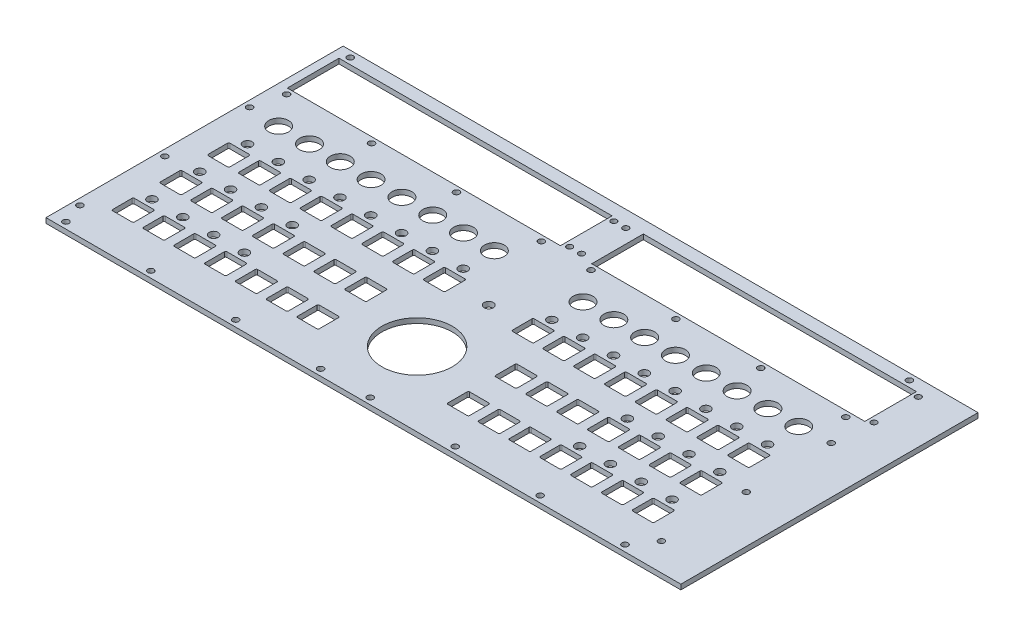
SolidWorks part; units mm, degrees
ref_plane "Front Plane" through (0, 0, 0) normal (0, 0, 1) x (1, 0, 0)
ref_plane "Top Plane" through (0, 0, 0) normal (0, 1, 0) x (1, 0, 0)
ref_plane "Right Plane" through (0, 0, 0) normal (1, 0, 0) x (0, 0, -1)
sketch "Sketch1" plane through (0, 0, 0) normal (0, 1, 0) x (1, 0, 0)
  line L1 (-41.8085, 33.4111) -> (338.0485, 33.4111)
  line L2 (-41.8085, 33.4111) -> (-41.8085, -144.3889)
  line L3 (-41.8085, -144.3889) -> (338.0485, -144.3889)
  line L4 (338.0485, 33.4111) -> (338.0485, -144.3889)
  dimension "D1" = 379.857
  dimension "D2" = 177.8
extrude "Boss-Extrude1" add sketch "Sketch1" along normal blind 3
sketch "Sketch2" plane through (0, 3, 0) normal (0, 1, 0) x (1, 0, 0)
  line L1 (-36.7674, 25.8724) -> (126.6333, 25.8724)
  line L2 (-36.7674, 25.8724) -> (-36.7674, -5.0267)
  line L3 (-36.7674, -5.0267) -> (126.6333, -5.0267)
  line L4 (126.6333, 25.8724) -> (126.6333, -5.0267)
  line L64 (-41.8085, 33.4111) -> (-41.8085, -144.3889) construction
  line L65 (-41.8085, -144.3889) -> (338.0485, -144.3889) construction
  line L66 (338.0485, 33.4111) -> (-41.8085, 33.4111) construction
  line L67 (145.3506, 25.8724) -> (308.7513, 25.8724)
  line L96 (308.7513, 25.8724) -> (308.7513, -5.0267)
  line L97 (145.3506, -5.0267) -> (308.7513, -5.0267)
  line L98 (145.3506, 25.8724) -> (145.3506, -5.0267)
  circle A0 centre (-19.5962, -27.399) radius 5.9207
  circle A1 centre (-1.1584, -27.399) radius 5.9207
  circle A2 centre (17.2795, -27.399) radius 5.9207
  circle A3 centre (35.7173, -27.399) radius 5.9207
  circle A4 centre (54.1552, -27.399) radius 5.9207
  circle A5 centre (72.5931, -27.399) radius 5.9207
  circle A6 centre (91.0309, -27.399) radius 5.9207
  circle A7 centre (109.4688, -27.399) radius 5.9207
  circle A8 centre (291.5868, -27.399) radius 5.9207
  circle A9 centre (273.1489, -27.399) radius 5.9207
  circle A10 centre (254.7111, -27.399) radius 5.9207
  circle A11 centre (236.2732, -27.399) radius 5.9207
  circle A12 centre (217.8353, -27.399) radius 5.9207
  circle A13 centre (199.3975, -27.399) radius 5.9207
  circle A14 centre (180.9596, -27.399) radius 5.9207
  circle A15 centre (162.5218, -27.399) radius 5.9207
  dimension "D8" = 11.8415
  dimension "D4" = 2
  dimension "D5" = 18.4379
  dimension "D6" = 22.2123
  dimension "D7" = 116.9899
  dimension "D17" = 30.8991
  dimension "D18" = 163.4007
  dimension "D19" = 5.0411
  dimension "D20" = 7.5387
  dimension "D2" = 3
  dimension "D3" = 8
  dimension "D16" = 3
  dimension "D26" = 2
extrude "Cut-Extrude1" cut sketch "Sketch2" against normal blind 10.16
sketch "Sketch4" plane through (0, 3, 0) normal (0, 1, 0) x (1, 0, 0)
  line L4 (-41.8085, 33.4111) -> (-41.8085, -144.3889) construction
  point P4 (-19.5962, -63.7796)
  line B0 (-25.3462, -50.7796) -> (-13.8462, -50.7796)
  line B1 (-26.0962, -51.5296) -> (-26.0962, -63.0296)
  line B2 (-25.3462, -63.7796) -> (-13.8462, -63.7796)
  line B3 (-13.0962, -51.5296) -> (-13.0962, -63.0296)
  arc B4 (-13.8462, -50.7796) -> (-13.0962, -51.5296) centre (-13.8462, -51.5296) cw
  arc B5 (-25.3462, -50.7796) -> (-26.0962, -51.5296) centre (-25.3462, -51.5296) ccw
  arc B6 (-13.8462, -63.7796) -> (-13.0962, -63.0296) centre (-13.8462, -63.0296) ccw
  arc B7 (-26.0962, -63.0296) -> (-25.3462, -63.7796) centre (-25.3462, -63.0296) ccw
  dimension "D1" = 22.2123
sketch_block_instance "Block1-1"
sketch_block "Block1" parameters "D1"=0.75, "D2"=0.75, "D3"=13
extrude "Cut-Extrude2" cut sketch "Sketch4" against normal blind 50.8
sketch "Sketch6" plane through (0, 3, 0) normal (0, 1, 0) x (1, 0, 0)
  line L0 (-41.8085, 33.4111) -> (-41.8085, -144.3889) construction
  line L1 (338.0485, 33.4111) -> (-41.8085, 33.4111) construction
  circle A0 centre (-19.5962, -46.0401) radius 2.667
  dimension "D1" = 5.334
  dimension "D2" = 22.2123
  dimension "D3" = 79.4512
extrude "Cut-Extrude3" cut sketch "Sketch6" against normal blind 50.8
pattern_linear "LPattern1" count 8 spacing 18.4375 along (1, 0, 0) count 3 spacing 28.575 along (0, 0, 1) skipping (4, 1), (4, 2), (5, 1), (5, 2), (6, 1), (6, 2), (7, 1), (7, 2) of "Cut-Extrude3"
pattern_linear "LPattern2" count 8 spacing 18.4375 along (1, 0, 0) count 3 spacing 28.575 along (0, 0, 1) skipping (7, 1), (7, 2) of "Cut-Extrude2"
sketch "Sketch7" plane through (0, 3, 0) normal (0, 1, 0) x (1, 0, 0)
  line L0 (338.0485, -144.3889) -> (338.0485, 33.4111) construction
  line L1 (298.0868, -63.7797) -> (285.0868, -63.7797)
  line L2 (298.0868, -63.7797) -> (298.0868, -50.7797)
  line L3 (298.0868, -50.7797) -> (285.0868, -50.7797)
  line L4 (285.0868, -63.7797) -> (285.0868, -50.7797)
  line L5 (298.0868, -63.7797) -> (285.0868, -50.7797) construction
  line L6 (298.0868, -50.7797) -> (285.0868, -63.7797) construction
  line L7 (338.0485, 33.4111) -> (-41.8085, 33.4111) construction
  point P0 (291.5868, -57.2797)
  dimension "D1" = 46.4617
  dimension "D2" = 13
  dimension "D3" = 13
  dimension "D4" = 84.1908
extrude "Cut-Extrude4" cut sketch "Sketch7" against normal blind 5.08
fillet "Fillet1" radius 0.7493 1 edges at (285.0868, 1.5, 50.7797)
fillet "Fillet2" radius 0.7493 3 edges at (298.0868, 1.5, 63.7797) (285.0868, 1.5, 63.7797) (298.0868, 1.5, 50.7797)
pattern_linear "LPattern3" count 8 spacing 18.4375 along (-1, 0, 0) count 3 spacing 28.575 along (0, 0, 1) skipping (7, 1), (7, 2) of "Cut-Extrude4", "Fillet1", "Fillet2"
sketch "Sketch9" plane through (0, 3, 0) normal (0, 1, 0) x (1, 0, 0)
  line L0 (174.4618, -80.104) -> (174.4618, -91.6054) construction
  line L1 (85.2788, -92.3546) -> (96.7788, -92.3546) construction
  circle A0 centre (135.9947, -100.1422) radius 21.0617
  dimension "D2" = 42.1234
  dimension "D1" = 38.467
  dimension "D3" = 7.7876
extrude "Cut-Extrude6" cut sketch "Sketch9" against normal blind 5.08
sketch "Sketch10" plane through (0, 3, 0) normal (0, 1, 0) x (1, 0, 0)
  line L0 (338.0485, 33.4111) -> (-41.8085, 33.4111) construction
  line L1 (297.3375, -50.7797) -> (285.8361, -50.7797) construction
  circle A0 centre (291.5868, -46.0401) radius 2.667
  point P4 (291.5868, -50.7797)
  dimension "D3" = 5.334
  dimension "D1" = 79.4512
  dimension "D2" = 0
extrude "Cut-Extrude7" cut sketch "Sketch10" against normal blind 5.08
pattern_linear "LPattern4" count 8 spacing 18.4375 along (-1, 0, 0) count 3 spacing 28.575 along (0, 0, 1) skipping (4, 1), (4, 2), (5, 1), (5, 2), (6, 1), (6, 2), (7, 1), (7, 2) of "Cut-Extrude7"
sketch "Sketch11" plane through (0, 3, 0) normal (0, 1, 0) x (1, 0, 0)
  line L0 (156.0243, -51.529) -> (156.0243, -63.0304) construction
  circle A0 centre (135.9951, -57.2797) radius 2.75
  point P4 (156.0243, -57.2797)
  dimension "D2" = 5.5
  dimension "D1" = 20.0292
  dimension "D3" = 0
extrude "Cut-Extrude8" cut sketch "Sketch11" against normal blind 5.08
sketch "Sketch12" plane through (0, 3, 0) normal (0, 1, 0) x (1, 0, 0)
  line L0 (-41.8085, 33.4111) -> (-41.8085, -144.3889) construction
  line L1 (-41.8085, -144.3889) -> (338.0485, -144.3889) construction
  circle A0 centre (-33.7085, -140.5789) radius 1.8288
  dimension "D1" = 3.6576
  dimension "D2" = 8.1001
  dimension "D3" = 3.81
extrude "Cut-Extrude9" cut sketch "Sketch12" against normal blind 5.08
pattern_linear "LPattern5" count 4 spacing 50.8 along (1, 0, 0) of "Cut-Extrude9"
sketch "Sketch13" plane through (0, 3, 0) normal (0, 1, 0) x (1, 0, 0)
  line L0 (-41.8085, 33.4111) -> (-41.8085, -144.3889) construction
  line L2 (338.0485, 33.4111) -> (-41.8085, 33.4111) construction
  circle A0 centre (-33.7085, 29.6011) radius 1.8288
  dimension "D1" = 3.6576
  dimension "D2" = 8.1001
  dimension "D3" = 3.81
extrude "Cut-Extrude10" cut sketch "Sketch13" against normal blind 5.08
pattern_linear "LPattern6" count 4 spacing 50.8 along (1, 0, 0) count 2 spacing 38.1 along (0, 0, 1) skipping (1, 0), (2, 0), (3, 0) of "Cut-Extrude10"
sketch "Sketch14" plane through (0, 3, 0) normal (0, 1, 0) x (1, 0, 0)
  line L0 (-41.8085, 33.4111) -> (-41.8085, -144.3889) construction
  line L1 (-41.8085, -144.3889) -> (338.0485, -144.3889) construction
  circle A0 centre (-38.057, -127.8789) radius 1.8288
  dimension "D1" = 3.6576
  dimension "D2" = 3.7516
  dimension "D3" = 16.51
extrude "Cut-Extrude11" cut sketch "Sketch14" against normal blind 5.08
pattern_linear "LPattern7" count 3 spacing 50.8 along (0, 0, -1) of "Cut-Extrude11"
sketch "Sketch15" plane through (0, 3, 0) normal (0, 1, 0) x (1, 0, 0)
  line L0 (338.0485, -144.3889) -> (338.0485, 33.4111) construction
  line L1 (-41.8085, -144.3889) -> (338.0485, -144.3889) construction
  circle A0 centre (300.8095, -140.5789) radius 1.8288
  dimension "D1" = 3.6576
  dimension "D2" = 37.2389
  dimension "D3" = 3.81
extrude "Cut-Extrude12" cut sketch "Sketch15" against normal blind 5.08
pattern_linear "LPattern8" count 4 spacing 50.8 along (-1, 0, 0) of "Cut-Extrude12"
sketch "Sketch16" plane through (0, 3, 0) normal (0, 1, 0) x (1, 0, 0)
  line L0 (338.0485, 33.4111) -> (-41.8085, 33.4111) construction
  line L1 (338.0485, -144.3889) -> (338.0485, 33.4111) construction
  circle A0 centre (300.8095, 29.6011) radius 1.8288
  dimension "D1" = 3.6576
  dimension "D2" = 3.81
  dimension "D3" = 37.2389
extrude "Cut-Extrude13" cut sketch "Sketch16" against normal blind 5.08
pattern_linear "LPattern9" count 4 spacing 50.8 along (-1, 0, 0) count 2 spacing 38.1 along (0, 0, 1) skipping (1, 0), (2, 0), (3, 0) of "Cut-Extrude13"
sketch "Sketch17" plane through (0, 3, 0) normal (0, 1, 0) x (1, 0, 0)
  line L0 (338.0485, -144.3889) -> (338.0485, 33.4111) construction
  line L1 (-41.8085, -144.3889) -> (338.0485, -144.3889) construction
  circle A0 centre (309.923, -127.8789) radius 1.8288
  dimension "D1" = 3.6576
  dimension "D2" = 28.1254
  dimension "D3" = 16.51
extrude "Cut-Extrude14" cut sketch "Sketch17" against normal blind 5.08
pattern_linear "LPattern10" count 3 spacing 50.8 along (0, 0, -1) of "Cut-Extrude14"
sketch "Sketch18" plane through (0, 3, 0) normal (0, 1, 0) x (1, 0, 0)
  line L0 (284.2311, -134.2671) -> (284.2311, -136.6871)
  line L2 (174.9378, -69.4113) -> (173.5407, -71.8313)
  line L3 (173.5407, -71.8313) -> (176.335, -71.8313)
  line L4 (163.1012, -71.0969) -> (164.4896, -73.5219)
  line L5 (164.4896, -73.5219) -> (165.8955, -71.107)
  line L6 (165.8955, -71.107) -> (163.1012, -71.0969)
  line L7 (258.5471, -128.088) -> (256.1271, -128.0949)
  line L8 (256.1271, -128.0949) -> (256.134, -130.5149)
  line L9 (256.134, -130.5149) -> (258.554, -130.508)
  line L10 (258.554, -130.508) -> (258.5471, -128.088)
  line L11 (269.6691, -128.6524) -> (267.5733, -127.4424)
  line L12 (267.5733, -127.4424) -> (267.5733, -129.8624)
  line L13 (267.5733, -129.8624) -> (269.6691, -128.6524)
  line L14 (284.2311, -136.6871) -> (285.4411, -135.4771)
  line L15 (285.4411, -135.4771) -> (284.2311, -134.2671)
  line L16 (285.4411, -134.2671) -> (285.4411, -136.6871)
  line L17 (285.4411, -136.6871) -> (286.6511, -135.4771)
  line L18 (286.6511, -135.4771) -> (285.4411, -134.2671)
  line L19 (176.335, -71.8313) -> (174.9378, -69.4113)
  line L20 (233.3826, -128.5904) -> (234.1893, -128.5904)
  line L21 (233.3826, -128.5904) -> (233.3826, -131.0104)
  line L22 (233.3826, -131.0104) -> (234.1893, -131.0104)
  line L23 (234.1893, -128.5904) -> (234.1893, -131.0104)
  line L24 (234.9959, -128.5904) -> (235.8026, -128.5904)
  line L25 (234.9959, -128.5904) -> (234.9959, -131.0104)
  line L26 (234.9959, -131.0104) -> (235.8026, -131.0104)
  line L27 (235.8026, -128.5904) -> (235.8026, -131.0104)
  line L39 (225.6455, -135.6501) -> (226.8486, -134.4332)
  line L40 (226.8624, -136.8532) -> (225.6455, -135.6501)
  line L41 (226.8486, -134.4332) -> (226.8624, -136.8532)
  line L42 (226.8555, -135.6432) -> (228.0586, -134.4264)
  line L43 (228.0723, -136.8463) -> (226.8555, -135.6432)
  line L44 (228.0586, -134.4264) -> (228.0723, -136.8463)
  circle A0 centre (174.9378, -71.0246) radius 0.8067 construction
  circle A1 centre (164.4954, -71.9086) radius 0.8067 construction
  circle A2 centre (257.3406, -129.3015) radius 1.21 construction
  circle A3 centre (268.2719, -128.6524) radius 0.6986 construction
  dimension "D1" = 2.42
  dimension "D2" = 2.42
  dimension "D3" = 2.42
  dimension "D4" = 2.42
  dimension "D5" = 0
  dimension "D6" = 2.42
  dimension "D7" = 2.42
  dimension "D8" = 1.21
  dimension "D9" = 1.21
  dimension "D10" = 2.42
  dimension "D11" = 2.42
  dimension "D12" = 0.8067
  dimension "D13" = 0.8067
  dimension "D14" = 0.8067
  dimension "D15" = 1.21
  dimension "D16" = 0
  dimension "D17" = 1.21
sketch "Sketch19" plane through (0, 0, 0) normal (0, -1, 0) x (1, 0, 0)
  circle A0 centre (312.051, -23.6727) radius 1.75
  circle A1 centre (312.051, 2.8273) radius 1.75
  circle A2 centre (137.051, -23.6727) radius 1.75
  circle A3 centre (137.051, 2.8273) radius 1.75
  circle A4 centre (129.9316, 2.8066) radius 1.7293
  circle A5 centre (129.9098, -23.6651) radius 1.7256
extrude "Cut-Extrude15" cut sketch "Sketch19" against normal blind 10
